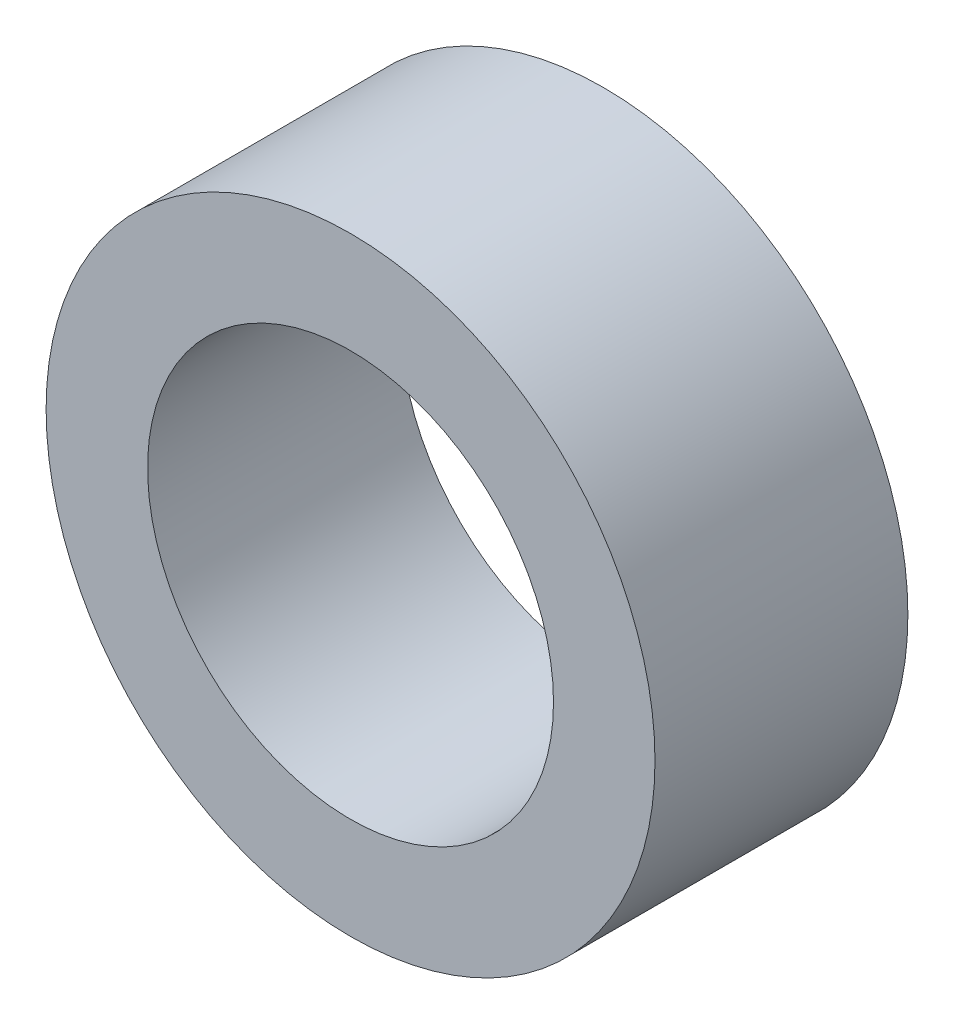
SolidWorks part; units mm, degrees
material "Delrin 2700 NC010, Low Viscosity Acetal Copolymer (SS)"
ref_plane "Front Plane" through (0, 0, 0) normal (0, 0, 1) x (1, 0, 0)
ref_plane "Top Plane" through (0, 0, 0) normal (0, 1, 0) x (1, 0, 0)
ref_plane "Right Plane" through (0, 0, 0) normal (1, 0, 0) x (0, 0, -1)
sketch "Sketch1" plane through (0, 0, 0) normal (0, 0, 1) x (1, 0, 0)
  line L0 (19.05, 0) -> (12.7, 0) construction
  line L1 (-19.05, 0) -> (19.05, 0) construction
  dimension "OD" = 38.1
  dimension "Wall Thickness" = 6.35
sketch "Sketch2" plane through (0, 0, 0) normal (1, 0, 0) x (0, 0, -1)
  line L0 (7.9125, 0) -> (-7.9125, 0)
  point P4 (0, 0)
  dimension "Length" = 15.825
sketch "Sketch3" plane through (0, 0, 0) normal (0, 0, 1) x (1, 0, 0)
  circle A0 centre (0, 0) radius 19.05
  circle A1 centre (0, 0) radius 12.7
extrude "Boss-Extrude1" add sketch "Sketch3" along normal up to vertex (7.9125 mm away) and the other way up to vertex (7.9125 mm away) up to point (0, 0, 7.9125) other way up to point (0, 0, -7.9125)
